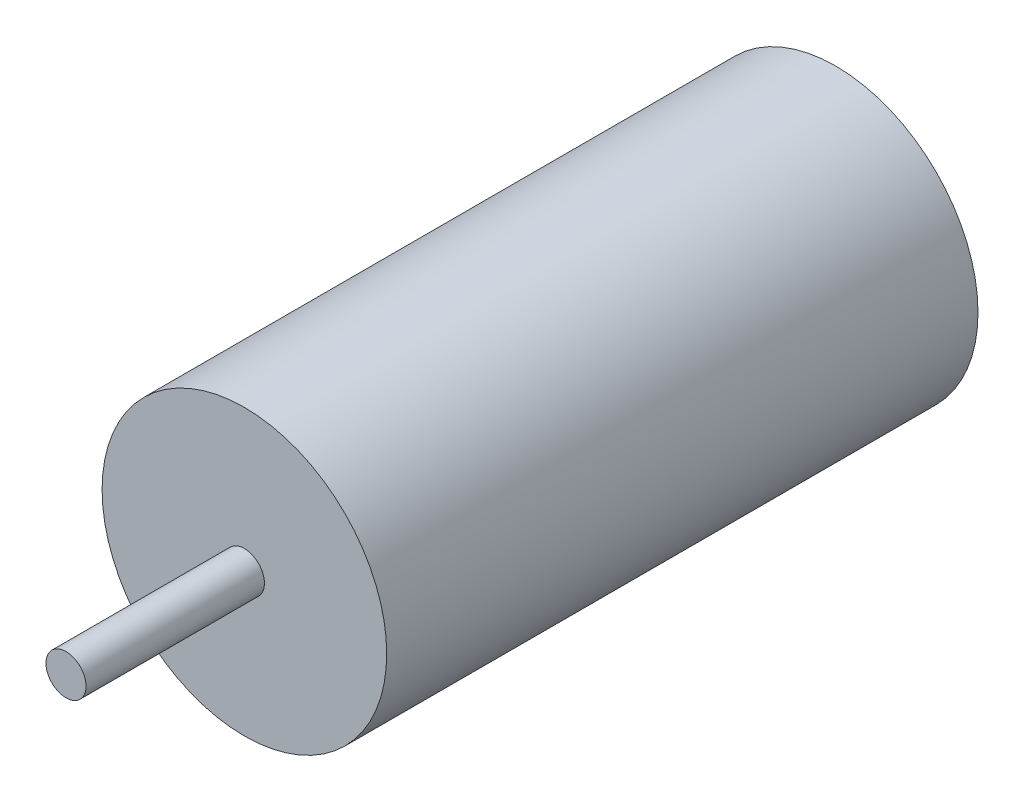
SolidWorks part; units mm, degrees
ref_plane "Front Plane" through (0, 0, 0) normal (0, 0, 1) x (1, 0, 0)
ref_plane "Top Plane" through (0, 0, 0) normal (0, 1, 0) x (1, 0, 0)
ref_plane "Right Plane" through (0, 0, 0) normal (1, 0, 0) x (0, 0, -1)
sketch "Sketch1" plane through (0, 0, 0) normal (0, 0, 1) x (1, 0, 0)
  circle A0 centre (0, 0) radius 14.2
  dimension "D1" = 28.4
extrude "Boss-Extrude1" add sketch "Sketch1" along normal blind 59
sketch "Sketch2" plane through (0, 0, 59) normal (0, 0, 1) x (1, 0, 0)
  circle A0 centre (0, 0) radius 2
  dimension "D1" = 4
extrude "Boss-Extrude2" add sketch "Sketch2" along normal blind 17.8
